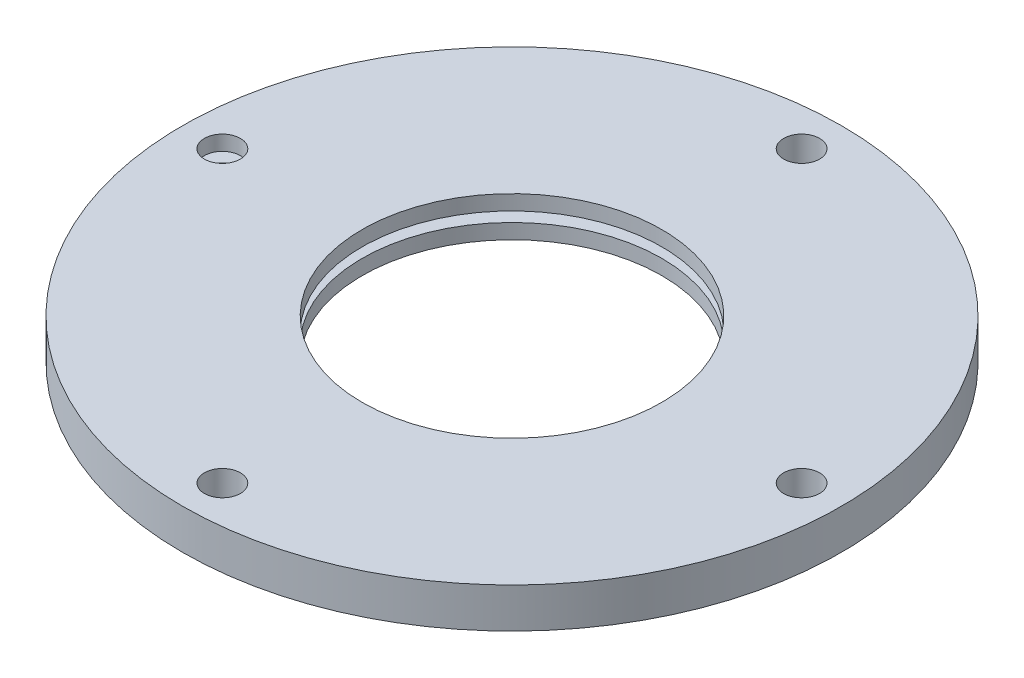
SolidWorks part; units mm, degrees
material "ABS"
ref_plane "Front Plane" through (0, 0, 0) normal (0, 0, 1) x (1, 0, 0)
ref_plane "Top Plane" through (0, 0, 0) normal (0, 1, 0) x (1, 0, 0)
ref_plane "Right Plane" through (0, 0, 0) normal (1, 0, 0) x (0, 0, -1)
sketch "Sketch1" plane through (0, 0, 0) normal (0, 1, 0) x (1, 0, 0)
  circle A0 centre (0, 0) radius 33
  circle A1 centre (-29, 0) radius 1.5
  circle A2 centre (0, 0) radius 29 construction
  circle A3 centre (0, 29) radius 1.5
  circle A4 centre (29, 0) radius 1.5
  circle A5 centre (0, -29) radius 1.5
  point P15 (0, 0)
  dimension "D1" = 66
  dimension "D2" = 4
  dimension "D3" = 3
  dimension "D4" = 4
extrude "Boss-Extrude1" add sketch "Sketch1" along normal blind 4
hole_wizard "CSK for M3 Flat Head Machine Screw1" positions "Sketch2" profile "Sketch3" countersink size "M3" standard "ANSI Metric" end condition through all
sketch "Sketch2" plane through (0, 0, 0) normal (0, -1, 0) x (-1, 0, 0)
  point P0 (0, -29)
  point P3 (29, 0)
  point P6 (0, 29)
  point P9 (-29, 0)
sketch "Sketch3" plane through (0, 0, 29) normal (1, 0, 0) x (0, 0, -1)
  line L0 (0, 0) -> (0, 4)
  line L1 (0, 4) -> (1.8, 4)
  line L2 (1.8, 4) -> (1.8, 1.35)
  line L3 (1.8, 1.35) -> (3.15, 0)
  line L5 (3.15, 0) -> (0, 0)
  line L6 (-1.8, 1.35) -> (-3.15, 0) construction
  line L11 (0, -6.35) -> (0, 107.95) construction
  dimension "Thru Hole Dia." = 3.6
  dimension "Thru Hole Depth" = 4
  dimension "Near C'Sink Dia." = 6.3
  dimension "Near C'Sink Angle" = 90
sketch "Croquis1" plane through (0, 0, 0) normal (0, -1, 0) x (1, 0, 0)
  circle A0 centre (0, 0) radius 15
  dimension "D1" = 30
extrude "Cortar-Extruir1" cut sketch "Croquis1" against normal up to next
ref_axis "Eje1" through (0, 4, 0) along (0, -1, 0)
ref_plane "Plano1" through (-33, 0, 0) normal (-1, 0, 0) x (0, 0, 1)
sketch "Croquis2" plane through (-33, 0, 0) normal (-1, 0, 0) x (0, 0, 1)
  line L0 (0, 0) -> (0, 4) construction
  line L1 (0, 4) -> (0, 0) construction
  line L3 (-20, 2.5) -> (20, 2.5)
  line L4 (-20, 2.5) -> (-20, 1.5)
  line L5 (-20, 1.5) -> (20, 1.5)
  line L6 (20, 2.5) -> (20, 1.5)
  line L7 (-20, 2.5) -> (20, 1.5) construction
  line L8 (-20, 1.5) -> (20, 2.5) construction
  line L10 (-33, 0) -> (33, 0) construction
  line L11 (33, 4) -> (-33, 4) construction
  point P5 (0, 2)
  point P10 (0, 0)
  dimension "D1" = 40
  dimension "D2" = 1
  dimension "D3" = 1.5
  dimension "D4" = 1.5
extrude "Cortar-Extruir2" cut sketch "Croquis2" against normal blind 50
